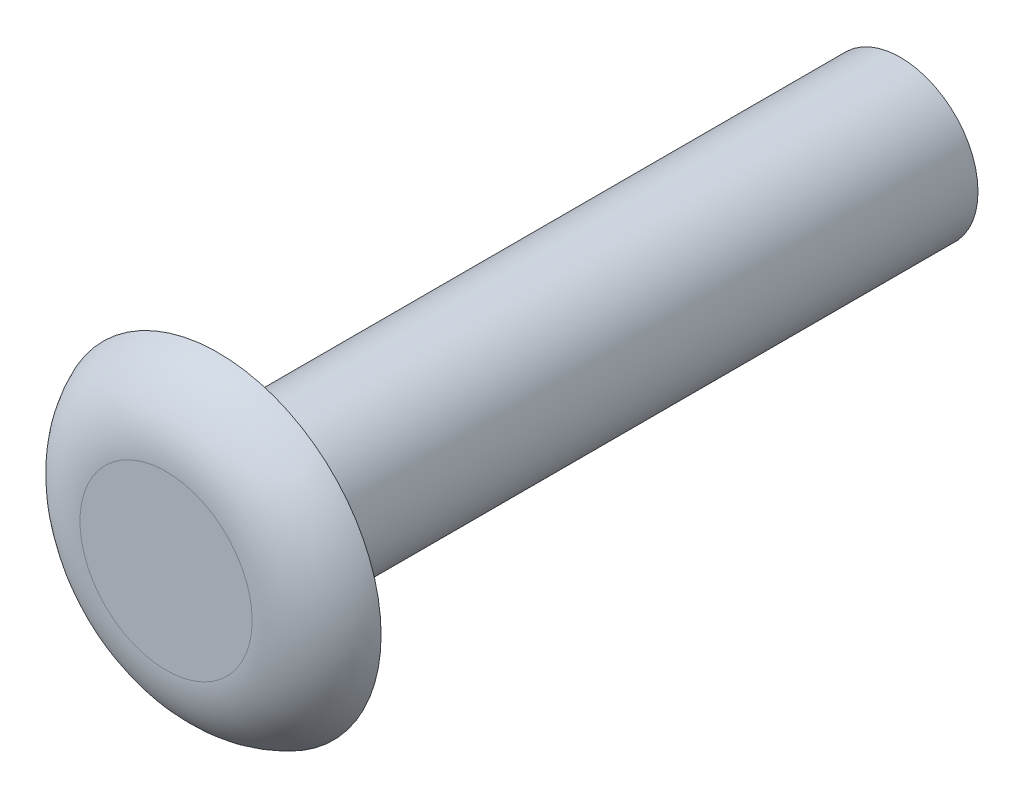
SolidWorks part; units mm, degrees
material "6061 Alloy"
ref_plane "Front Plane" through (0, 0, 0) normal (0, 0, 1) x (1, 0, 0)
ref_plane "Top Plane" through (0, 0, 0) normal (0, 1, 0) x (1, 0, 0)
ref_plane "Right Plane" through (0, 0, 0) normal (1, 0, 0) x (0, 0, -1)
sketch "Sketch1" plane through (0, 0, 0) normal (0, 0, 1) x (1, 0, 0)
  circle A0 centre (0, 0) radius 5.0038
  dimension "D1" = 10.0076
extrude "Boss-Extrude1" add sketch "Sketch1" along normal blind 1.6002
sketch "Sketch2" plane through (0, 0, 0) normal (0, 0, 1) x (1, 0, 0)
  circle A0 centre (0, 0) radius 2.3813
  dimension "D1" = 4.7625
extrude "Boss-Extrude2" add sketch "Sketch2" against normal blind 20.955
fillet "Fillet1" radius 2.54 1 edges at (5.0038, 0, 1.6002)
